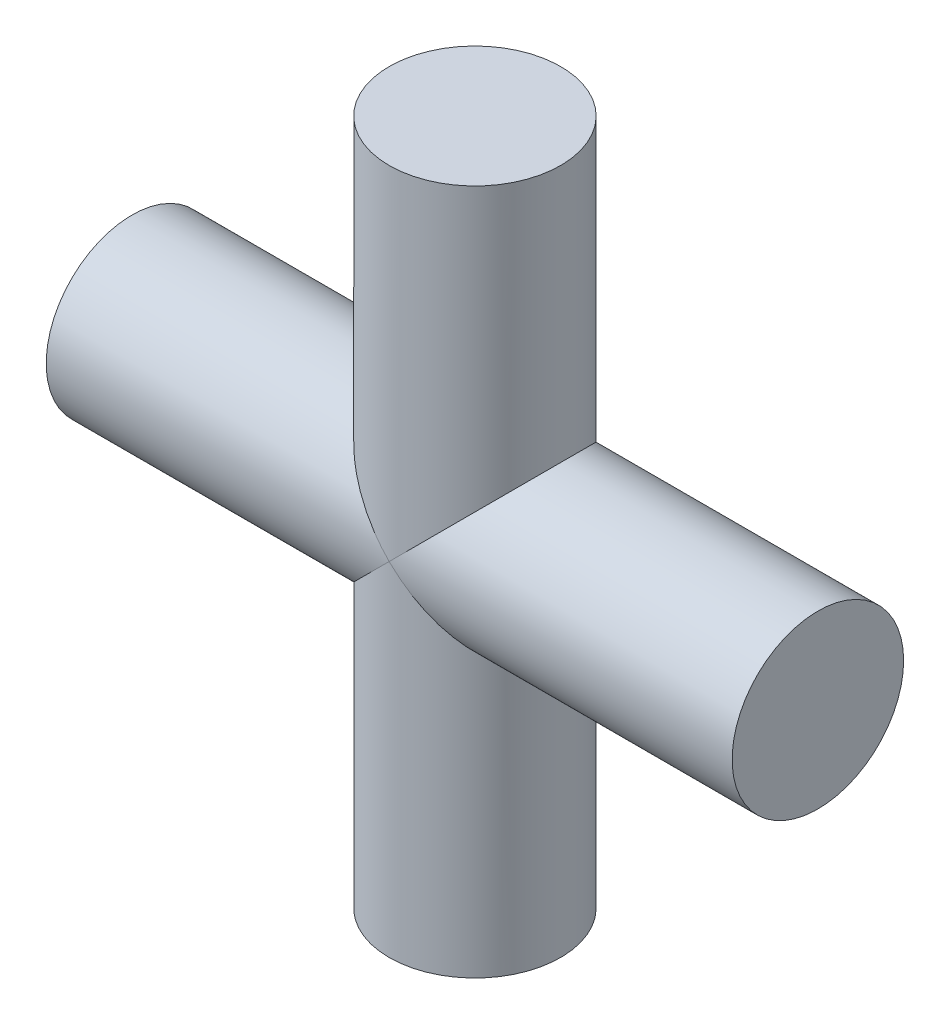
SolidWorks part; units mm, degrees
ref_plane "Front Plane" through (0, 0, 0) normal (0, 0, 1) x (1, 0, 0)
ref_plane "Top Plane" through (0, 0, 0) normal (0, 1, 0) x (1, 0, 0)
ref_plane "Right Plane" through (0, 0, 0) normal (1, 0, 0) x (0, 0, -1)
sketch "Sketch1" plane through (0, 0, 0) normal (1, 0, 0) x (0, 0, -1)
  circle A0 centre (0, 0) radius 5
  dimension "D1" = 10
extrude "Boss-Extrude1" add sketch "Sketch1" along normal blind 20 and the other way blind 20
sketch "Sketch2" plane through (0, 0, 0) normal (0, 1, 0) x (1, 0, 0)
  circle A0 centre (0, 0) radius 5
extrude "Boss-Extrude2" add sketch "Sketch2" along normal blind 20 and the other way blind 20
sketch3d "3DSketch1"
  line L0 (-20, 0, 0) -> (20, 0, 0) construction
  line L1 (-20, 0, 0) -> (0, 0, 0) construction
  line L2 (0, 0, 0) -> (20, 0, 0) construction
  line L3 (0, -20, 0) -> (0, 20, 0) construction
  line L4 (0, -20, 0) -> (0, 0, 0) construction
  line L5 (0, 0, 0) -> (0, 20, 0) construction
  point P12 (0, 0, 0)
